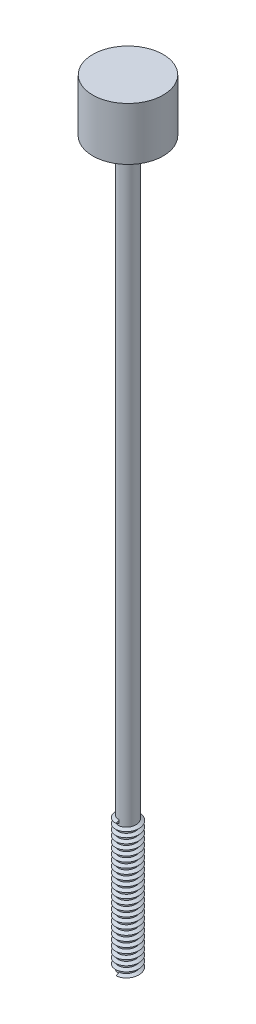
SolidWorks part; units mm, degrees
ref_plane "Front Plane" through (0, 0, 0) normal (0, 0, 1) x (1, 0, 0)
ref_plane "Top Plane" through (0, 0, 0) normal (0, 1, 0) x (1, 0, 0)
ref_plane "Right Plane" through (0, 0, 0) normal (1, 0, 0) x (0, 0, -1)
sketch "Sketch1" plane through (0, 0, 0) normal (0, 1, 0) x (1, 0, 0)
  circle A0 centre (0, 0) radius 5
extrude "Boss-Extrude1" add sketch "Sketch1" along normal blind 320 and the other way blind 90
sketch "Sketch2" plane through (0, 320, 0) normal (0, 1, 0) x (1, 0, 0)
  circle A0 centre (0, 0) radius 20
extrude "Boss-Extrude2" add sketch "Sketch2" along normal blind 30
sketch "Sketch3" plane through (0, -90, 0) normal (0, -1, 0) x (1, 0, 0)
  circle A0 centre (0, 0) radius 5
curve "Helix/Spiral1" pitch 3 height 75 radius 5 centre (0, -90, 0) axis (0, 1, 0) start towards (0, 0, 1)
sketch "Sketch4" plane through (0, 0, 0) normal (1, 0, 0) x (0, 0, -1)
  line L1 (-6.7, -75) -> (-4.15, -76.4722)
  line L2 (-4.15, -76.4722) -> (-4.15, -73.5278)
  line L3 (-4.15, -73.5278) -> (-6.7, -75)
  circle A0 centre (-5, -75) radius 0.85 construction
  spline S0 degree 3 poles (-5, -90) (-5, -89.9379) (-4.7397, -89.8123) (-3.6276, -89.625) (-1.9632, -89.4375) (0, -89.25) (1.9632, -89.0625) (3.6276, -88.875) (4.7397, -88.6875) (5.1302, -88.5) (4.7397, -88.3125) (3.6276, -88.125) (1.9632, -87.9375) (0, -87.75) (-1.9632, -87.5625) (-3.6276, -87.375) (-4.7397, -87.1875) (-5.1302, -87) (-4.7397, -86.8125) (-3.6276, -86.625) (-1.9632, -86.4375) (0, -86.25) (1.9632, -86.0625) (3.6276, -85.875) (4.7397, -85.6875) (5.1302, -85.5) (4.7397, -85.3125) (3.6276, -85.125) (1.9632, -84.9375) (0, -84.75) (-1.9632, -84.5625) (-3.6276, -84.375) (-4.7397, -84.1875) (-5.1302, -84) (-4.7397, -83.8125) (-3.6276, -83.625) (-1.9632, -83.4375) (0, -83.25) (1.9632, -83.0625) (3.6276, -82.875) (4.7397, -82.6875) (5.1302, -82.5) (4.7397, -82.3125) (3.6276, -82.125) (1.9632, -81.9375) (0, -81.75) (-1.9632, -81.5625) (-3.6276, -81.375) (-4.7397, -81.1875) (-5.1302, -81) (-4.7397, -80.8125) (-3.6276, -80.625) (-1.9632, -80.4375) (0, -80.25) (1.9632, -80.0625) (3.6276, -79.875) (4.7397, -79.6875) (5.1302, -79.5) (4.7397, -79.3125) (3.6276, -79.125) (1.9632, -78.9375) (0, -78.75) (-1.9632, -78.5625) (-3.6276, -78.375) (-4.7397, -78.1875) (-5.1302, -78) (-4.7397, -77.8125) (-3.6276, -77.625) (-1.9632, -77.4375) (0, -77.25) (1.9632, -77.0625) (3.6276, -76.875) (4.7397, -76.6875) (5.1302, -76.5) (4.7397, -76.3125) (3.6276, -76.125) (1.9632, -75.9375) (0, -75.75) (-1.9632, -75.5625) (-3.6276, -75.375) (-4.7397, -75.1875) (-5.1302, -75) (-4.7397, -74.8125) (-3.6276, -74.625) (-1.9632, -74.4375) (0, -74.25) (1.9632, -74.0625) (3.6276, -73.875) (4.7397, -73.6875) (5.1302, -73.5) (4.7397, -73.3125) (3.6276, -73.125) (1.9632, -72.9375) (0, -72.75) (-1.9632, -72.5625) (-3.6276, -72.375) (-4.7397, -72.1875) (-5.1302, -72) (-4.7397, -71.8125) (-3.6276, -71.625) (-1.9632, -71.4375) (0, -71.25) (1.9632, -71.0625) (3.6276, -70.875) (4.7397, -70.6875) (5.1302, -70.5) (4.7397, -70.3125) (3.6276, -70.125) (1.9632, -69.9375) (0, -69.75) (-1.9632, -69.5625) (-3.6276, -69.375) (-4.7397, -69.1875) (-5.1302, -69) (-4.7397, -68.8125) (-3.6276, -68.625) (-1.9632, -68.4375) (0, -68.25) (1.9632, -68.0625) (3.6276, -67.875) (4.7397, -67.6875) (5.1302, -67.5) (4.7397, -67.3125) (3.6276, -67.125) (1.9632, -66.9375) (0, -66.75) (-1.9632, -66.5625) (-3.6276, -66.375) (-4.7397, -66.1875) (-5.1302, -66) (-4.7397, -65.8125) (-3.6276, -65.625) (-1.9632, -65.4375) (0, -65.25) (1.9632, -65.0625) (3.6276, -64.875) (4.7397, -64.6875) (5.1302, -64.5) (4.7397, -64.3125) (3.6276, -64.125) (1.9632, -63.9375) (0, -63.75) (-1.9632, -63.5625) (-3.6276, -63.375) (-4.7397, -63.1875) (-5.1302, -63) (-4.7397, -62.8125) (-3.6276, -62.625) (-1.9632, -62.4375) (0, -62.25) (1.9632, -62.0625) (3.6276, -61.875) (4.7397, -61.6875) (5.1302, -61.5) (4.7397, -61.3125) (3.6276, -61.125) (1.9632, -60.9375) (0, -60.75) (-1.9632, -60.5625) (-3.6276, -60.375) (-4.7397, -60.1875) (-5.1302, -60) (-4.7397, -59.8125) (-3.6276, -59.625) (-1.9632, -59.4375) (0, -59.25) (1.9632, -59.0625) (3.6276, -58.875) (4.7397, -58.6875) (5.1302, -58.5) (4.7397, -58.3125) (3.6276, -58.125) (1.9632, -57.9375) (0, -57.75) (-1.9632, -57.5625) (-3.6276, -57.375) (-4.7397, -57.1875) (-5.1302, -57) (-4.7397, -56.8125) (-3.6276, -56.625) (-1.9632, -56.4375) (0, -56.25) (1.9632, -56.0625) (3.6276, -55.875) (4.7397, -55.6875) (5.1302, -55.5) (4.7397, -55.3125) (3.6276, -55.125) (1.9632, -54.9375) (0, -54.75) (-1.9632, -54.5625) (-3.6276, -54.375) (-4.7397, -54.1875) (-5.1302, -54) (-4.7397, -53.8125) (-3.6276, -53.625) (-1.9632, -53.4375) (0, -53.25) (1.9632, -53.0625) (3.6276, -52.875) (4.7397, -52.6875) (5.1302, -52.5) (4.7397, -52.3125) (3.6276, -52.125) (1.9632, -51.9375) (0, -51.75) (-1.9632, -51.5625) (-3.6276, -51.375) (-4.7397, -51.1875) (-5.1302, -51) (-4.7397, -50.8125) (-3.6276, -50.625) (-1.9632, -50.4375) (0, -50.25) (1.9632, -50.0625) (3.6276, -49.875) (4.7397, -49.6875) (5.1302, -49.5) (4.7397, -49.3125) (3.6276, -49.125) (1.9632, -48.9375) (0, -48.75) (-1.9632, -48.5625) (-3.6276, -48.375) (-4.7397, -48.1875) (-5.1302, -48) (-4.7397, -47.8125) (-3.6276, -47.625) (-1.9632, -47.4375) (0, -47.25) (1.9632, -47.0625) (3.6276, -46.875) (4.7397, -46.6875) (5.1302, -46.5) (4.7397, -46.3125) (3.6276, -46.125) (1.9632, -45.9375) (0, -45.75) (-1.9632, -45.5625) (-3.6276, -45.375) (-4.7397, -45.1875) (-5.1302, -45) (-4.7397, -44.8125) (-3.6276, -44.625) (-1.9632, -44.4375) (0, -44.25) (1.9632, -44.0625) (3.6276, -43.875) (4.7397, -43.6875) (5.1302, -43.5) (4.7397, -43.3125) (3.6276, -43.125) (1.9632, -42.9375) (0, -42.75) (-1.9632, -42.5625) (-3.6276, -42.375) (-4.7397, -42.1875) (-5.1302, -42) (-4.7397, -41.8125) (-3.6276, -41.625) (-1.9632, -41.4375) (0, -41.25) (1.9632, -41.0625) (3.6276, -40.875) (4.7397, -40.6875) (5.1302, -40.5) (4.7397, -40.3125) (3.6276, -40.125) (1.9632, -39.9375) (0, -39.75) (-1.9632, -39.5625) (-3.6276, -39.375) (-4.7397, -39.1875) (-5.1302, -39) (-4.7397, -38.8125) (-3.6276, -38.625) (-1.9632, -38.4375) (0, -38.25) (1.9632, -38.0625) (3.6276, -37.875) (4.7397, -37.6875) (5.1302, -37.5) (4.7397, -37.3125) (3.6276, -37.125) (1.9632, -36.9375) (0, -36.75) (-1.9632, -36.5625) (-3.6276, -36.375) (-4.7397, -36.1875) (-5.1302, -36) (-4.7397, -35.8125) (-3.6276, -35.625) (-1.9632, -35.4375) (0, -35.25) (1.9632, -35.0625) (3.6276, -34.875) (4.7397, -34.6875) (5.1302, -34.5) (4.7397, -34.3125) (3.6276, -34.125) (1.9632, -33.9375) (0, -33.75) (-1.9632, -33.5625) (-3.6276, -33.375) (-4.7397, -33.1875) (-5.1302, -33) (-4.7397, -32.8125) (-3.6276, -32.625) (-1.9632, -32.4375) (0, -32.25) (1.9632, -32.0625) (3.6276, -31.875) (4.7397, -31.6875) (5.1302, -31.5) (4.7397, -31.3125) (3.6276, -31.125) (1.9632, -30.9375) (0, -30.75) (-1.9632, -30.5625) (-3.6276, -30.375) (-4.7397, -30.1875) (-5.1302, -30) (-4.7397, -29.8125) (-3.6276, -29.625) (-1.9632, -29.4375) (0, -29.25) (1.9632, -29.0625) (3.6276, -28.875) (4.7397, -28.6875) (5.1302, -28.5) (4.7397, -28.3125) (3.6276, -28.125) (1.9632, -27.9375) (0, -27.75) (-1.9632, -27.5625) (-3.6276, -27.375) (-4.7397, -27.1875) (-5.1302, -27) (-4.7397, -26.8125) (-3.6276, -26.625) (-1.9632, -26.4375) (0, -26.25) (1.9632, -26.0625) (3.6276, -25.875) (4.7397, -25.6875) (5.1302, -25.5) (4.7397, -25.3125) (3.6276, -25.125) (1.9632, -24.9375) (0, -24.75) (-1.9632, -24.5625) (-3.6276, -24.375) (-4.7397, -24.1875) (-5.1302, -24) (-4.7397, -23.8125) (-3.6276, -23.625) (-1.9632, -23.4375) (0, -23.25) (1.9632, -23.0625) (3.6276, -22.875) (4.7397, -22.6875) (5.1302, -22.5) (4.7397, -22.3125) (3.6276, -22.125) (1.9632, -21.9375) (0, -21.75) (-1.9632, -21.5625) (-3.6276, -21.375) (-4.7397, -21.1875) (-5.1302, -21) (-4.7397, -20.8125) (-3.6276, -20.625) (-1.9632, -20.4375) (0, -20.25) (1.9632, -20.0625) (3.6276, -19.875) (4.7397, -19.6875) (5.1302, -19.5) (4.7397, -19.3125) (3.6276, -19.125) (1.9632, -18.9375) (0, -18.75) (-1.9632, -18.5625) (-3.6276, -18.375) (-4.7397, -18.1875) (-5.1302, -18) (-4.7397, -17.8125) (-3.6276, -17.625) (-1.9632, -17.4375) (0, -17.25) (1.9632, -17.0625) (3.6276, -16.875) (4.7397, -16.6875) (5.1302, -16.5) (4.7397, -16.3125) (3.6276, -16.125) (1.9632, -15.9375) (0, -15.75) (-1.9632, -15.5625) (-3.6276, -15.375) (-4.7397, -15.1877) (-5, -15.0621) (-5, -15) knots 0 0 0 0 0.0025 0.005 0.0075 0.01 0.0125 0.015 0.0175 0.02 0.0225 0.025 0.0275 0.03 0.0325 0.035 0.0375 0.04 0.0425 0.045 0.0475 0.05 0.0525 0.055 0.0575 0.06 0.0625 0.065 0.0675 0.07 0.0725 0.075 0.0775 0.08 0.0825 0.085 0.0875 0.09 0.0925 0.095 0.0975 0.1 0.1025 0.105 0.1075 0.11 0.1125 0.115 0.1175 0.12 0.1225 0.125 0.1275 0.13 0.1325 0.135 0.1375 0.14 0.1425 0.145 0.1475 0.15 0.1525 0.155 0.1575 0.16 0.1625 0.165 0.1675 0.17 0.1725 0.175 0.1775 0.18 0.1825 0.185 0.1875 0.19 0.1925 0.195 0.1975 0.2 0.2025 0.205 0.2075 0.21 0.2125 0.215 0.2175 0.22 0.2225 0.225 0.2275 0.23 0.2325 0.235 0.2375 0.24 0.2425 0.245 0.2475 0.25 0.2525 0.255 0.2575 0.26 0.2625 0.265 0.2675 0.27 0.2725 0.275 0.2775 0.28 0.2825 0.285 0.2875 0.29 0.2925 0.295 0.2975 0.3 0.3025 0.305 0.3075 0.31 0.3125 0.315 0.3175 0.32 0.3225 0.325 0.3275 0.33 0.3325 0.335 0.3375 0.34 0.3425 0.345 0.3475 0.35 0.3525 0.355 0.3575 0.36 0.3625 0.365 0.3675 0.37 0.3725 0.375 0.3775 0.38 0.3825 0.385 0.3875 0.39 0.3925 0.395 0.3975 0.4 0.4025 0.405 0.4075 0.41 0.4125 0.415 0.4175 0.42 0.4225 0.425 0.4275 0.43 0.4325 0.435 0.4375 0.44 0.4425 0.445 0.4475 0.45 0.4525 0.455 0.4575 0.46 0.4625 0.465 0.4675 0.47 0.4725 0.475 0.4775 0.48 0.4825 0.485 0.4875 0.49 0.4925 0.495 0.4975 0.5 0.5025 0.505 0.5075 0.51 0.5125 0.515 0.5175 0.52 0.5225 0.525 0.5275 0.53 0.5325 0.535 0.5375 0.54 0.5425 0.545 0.5475 0.55 0.5525 0.555 0.5575 0.56 0.5625 0.565 0.5675 0.57 0.5725 0.575 0.5775 0.58 0.5825 0.585 0.5875 0.59 0.5925 0.595 0.5975 0.6 0.6025 0.605 0.6075 0.61 0.6125 0.615 0.6175 0.62 0.6225 0.625 0.6275 0.63 0.6325 0.635 0.6375 0.64 0.6425 0.645 0.6475 0.65 0.6525 0.655 0.6575 0.66 0.6625 0.665 0.6675 0.67 0.6725 0.675 0.6775 0.68 0.6825 0.685 0.6875 0.69 0.6925 0.695 0.6975 0.7 0.7025 0.705 0.7075 0.71 0.7125 0.715 0.7175 0.72 0.7225 0.725 0.7275 0.73 0.7325 0.735 0.7375 0.74 0.7425 0.745 0.7475 0.75 0.7525 0.755 0.7575 0.76 0.7625 0.765 0.7675 0.77 0.7725 0.775 0.7775 0.78 0.7825 0.785 0.7875 0.79 0.7925 0.795 0.7975 0.8 0.8025 0.805 0.8075 0.81 0.8125 0.815 0.8175 0.82 0.8225 0.825 0.8275 0.83 0.8325 0.835 0.8375 0.84 0.8425 0.845 0.8475 0.85 0.8525 0.855 0.8575 0.86 0.8625 0.865 0.8675 0.87 0.8725 0.875 0.8775 0.88 0.8825 0.885 0.8875 0.89 0.8925 0.895 0.8975 0.9 0.9025 0.905 0.9075 0.91 0.9125 0.915 0.9175 0.92 0.9225 0.925 0.9275 0.93 0.9325 0.935 0.9375 0.94 0.9425 0.945 0.9475 0.95 0.9525 0.955 0.9575 0.96 0.9625 0.965 0.9675 0.97 0.9725 0.975 0.9775 0.98 0.9825 0.985 0.9875 0.99 0.9925 0.995 0.9975 1 1 1 1 construction
sweep "Sweep1" add profiles "Sketch4" path "Helix/Spiral1"
sketch "Sketch5" plane through (0, 0, 0) normal (1, 0, 0) x (0, 0, -1)
  line L1 (5, -90) -> (-8.4252, -90)
  line L2 (5, -90) -> (5, -152.2459)
  line L3 (5, -152.2459) -> (-8.4252, -152.2459)
  line L4 (-8.4252, -90) -> (-8.4252, -152.2459)
extrude "Cut-Extrude1" cut sketch "Sketch5" against normal blind 30 and the other way blind 30
